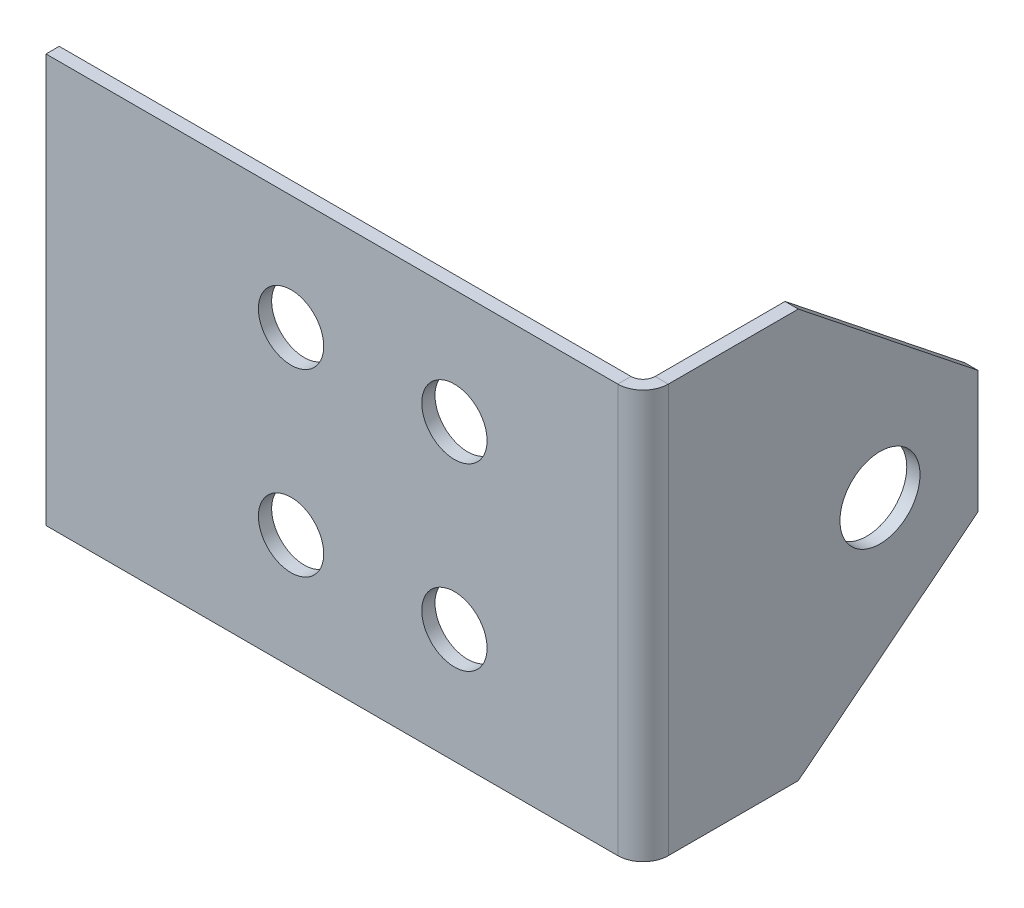
SolidWorks part; units mm, degrees
note: The reader was unsure of these and kept them because the rebuilt part matched: flange length of "Edge-Flange1".
ref_plane "Front Plane" through (0, 0, 0) normal (0, 0, 1) x (1, 0, 0)
ref_plane "Top Plane" through (0, 0, 0) normal (0, 1, 0) x (1, 0, 0)
ref_plane "Right Plane" through (0, 0, 0) normal (1, 0, 0) x (0, 0, -1)
sketch "Sketch1" plane through (0, 0, 0) normal (0, 0, 1) x (1, 0, 0)
  line L1 (0, 0) -> (35, 0)
  line L2 (0, 0) -> (0, 25)
  line L3 (0, 25) -> (35, 25)
  line L4 (35, 0) -> (35, 25)
  dimension "D1" = 25
  dimension "D2" = 35
base flange "Base-Flange1" sketch "Sketch1" thickness 0.81 reverse thickness direction no parameters "D1"=0.7366
edge flange "Edge-Flange1" sketch "Sketch8" flange angle 90 flange length 35 flange position bend outside bend radius 0.7366 thickness 0.81 relief rectangular parameters "D6"=10
sketch "Sketch8" plane through (35, 0, -0.81) normal (-1, 0, 0) x (0, 1, 0)
  line L1 (25, 0) -> (0, 0) construction
  line L2 (0, 0) -> (0, 34.19)
  line L3 (0, 34.19) -> (25, 34.19)
  line L4 (25, 34.19) -> (25, 0)
  line L5 (25, 0) -> (0, 0)
bend "EdgeBend1" bend radius 0.7366 bend angle 90 parameters "D5"=1
sketch "Sketch9" plane through (0, 0, -0.81) normal (0, 0, -1) x (-1, 0, 0)
  line L0 (-35, 12.5) -> (0, 12.5) construction
  line L1 (-35, 0) -> (-35, 25) construction
  line L2 (0, 25) -> (0, 0) construction
  line L4 (-20, 25) -> (-20, 0) construction
  line L5 (-35, 25) -> (0, 25) construction
  line L6 (0, 0) -> (-35, 0) construction
  circle A0 centre (-25, 18) radius 2
  circle A1 centre (-25, 7) radius 2
  circle A2 centre (-15, 18) radius 2
  circle A3 centre (-15, 7) radius 2
  dimension "D1" = 4
  dimension "D2" = 15
  dimension "D3" = 7
  dimension "D4" = 5
extrude "Cut-Extrude1" cut sketch "Sketch9" against normal up to next normal cut yes
sketch "Sketch11" plane through (35.7366, 0, 0) normal (-1, 0, 0) x (0, 0, 1)
  line L0 (-24.0123, 12.5) -> (-1.5466, 12.5) construction
  line L1 (-9.5, 25) -> (-20.5, 16.25)
  line L2 (-1.5466, 25) -> (-1.5466, 0) construction
  line L3 (-14.5, 25) -> (-14.5, 0) construction
  line L4 (-1.5466, 25) -> (-35, 25) construction
  line L5 (-35, 0) -> (-1.5466, 0) construction
  line L6 (-39.5, 25) -> (-39.5, 0)
  line L7 (-39.5, 25) -> (-14.5, 25)
  line L8 (0, 0) -> (0, 25) construction
  line L9 (-39.5, 0) -> (-14.5, 0)
  line L10 (-20.5, 16.25) -> (-20.5, 8.75)
  line L11 (-20.5, 8.75) -> (-9.5, 0)
  line L12 (-9.5, 0) -> (-14.5, 0)
  line L13 (-14.5, 25) -> (-9.5, 25)
  circle A0 centre (-14.5, 12.5) radius 2.45
  dimension "D2" = 4.9
  dimension "D4" = 5
  dimension "D5" = 6
  dimension "D1" = 14.5
  dimension "D3" = 25
  dimension "D6" = 7.5
extrude "Cut-Extrude2" cut sketch "Sketch11" against normal up to next normal cut yes
sketch "Bend-Lines1" plane through (0, 0, 0) normal (0, 1, 0) x (1, 0, 0)
sketch "Bounding-Box1" plane through (0, 0, 0) normal (0, 1, 0) x (1, 0, 0)
sheet metal parameters "Sheet-Metal1" thickness 0.81 parameters "D1"=0.7366
flat pattern "Flat-Pattern1" [suppressed]
sketch "Bend-Lines2" plane through (0, 0, 0) normal (0, 1, 0) x (1, 0, 0)
sketch "Bounding-Box2" [suppressed] plane through (0, 0, 0) normal (0, 1, 0) x (1, 0, 0)
sheet metal parameters "Sheet-Metal2" thickness 0.81 parameters "D1"=0.7366
flat pattern "Flat-Pattern1" [suppressed]
sketch "Bend-Lines2" plane through (0, 0, 0) normal (0, 1, 0) x (1, 0, 0)
sketch "Bounding-Box2" [suppressed] plane through (0, 0, 0) normal (0, 1, 0) x (1, 0, 0)
bend of the flat pattern "Flatten-<EdgeBend1>1"
sheet metal parameters "Sheet-Metal3" thickness 0.81 parameters "D1"=0.7366
flat pattern "Flat-Pattern1" [suppressed]
sketch "Bend-Lines2" plane through (0, 0, 0) normal (0, 1, 0) x (1, 0, 0)
sketch "Bounding-Box2" [suppressed] plane through (0, 0, 0) normal (0, 1, 0) x (1, 0, 0)
bend of the flat pattern "Flatten-<EdgeBend1>1"
sheet metal parameters "Sheet-Metal4" thickness 0.81 parameters "D1"=0.7366
flat pattern "Flat-Pattern1" [suppressed]
sketch "Bend-Lines2" plane through (0, 0, 0) normal (0, 1, 0) x (1, 0, 0)
sketch "Bounding-Box2" [suppressed] plane through (0, 0, 0) normal (0, 1, 0) x (1, 0, 0)
bend of the flat pattern "Flatten-<EdgeBend1>1"
